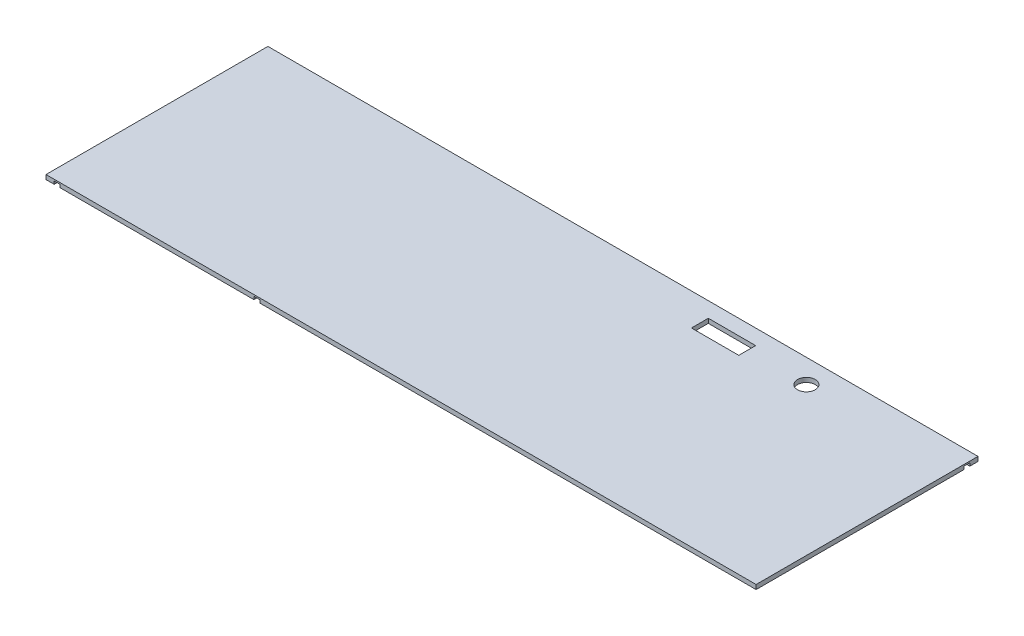
SolidWorks part; units mm, degrees
material "Oak"
ref_plane "Front Plane" through (0, 0, 0) normal (0, 0, 1) x (1, 0, 0)
ref_plane "Top Plane" through (0, 0, 0) normal (0, 1, 0) x (1, 0, 0)
ref_plane "Right Plane" through (0, 0, 0) normal (1, 0, 0) x (0, 0, -1)
sketch "Sketch1" plane through (0, 0, 0) normal (0, 1, 0) x (1, 0, 0)
  line L0 (800, 375) -> (800, -375) construction
  line L1 (-1200, -375) -> (1200, -375)
  line L2 (-1200, -375) -> (-1200, 375)
  line L3 (-1200, 375) -> (1200, 375)
  line L4 (1200, -375) -> (1200, 375)
  line L5 (-1200, -375) -> (1200, 375) construction
  line L6 (-1200, 375) -> (1200, -375) construction
  line L7 (-450, 375) -> (-450, -375) construction
  line L9 (500, 266.5) -> (340, 266.5)
  line L10 (500, 266.5) -> (500, 323.5)
  line L11 (500, 323.5) -> (340, 323.5)
  line L12 (340, 266.5) -> (340, 323.5)
  circle A0 centre (700, 295) radius 30
  point P0 (0, 0)
  point P16 (500, 295)
  dimension "D6" = 60
  dimension "D1" = 2400
  dimension "D2" = 750
  dimension "D3" = 750
  dimension "D4" = 400
  dimension "D5" = 1250
  dimension "D7" = 160
  dimension "D8" = 57
  dimension "D9" = 80
  dimension "D10" = 100
  dimension "D11" = 300
extrude "Boss-Extrude1" add sketch "Sketch1" along normal blind 15
sketch "Sketch2" plane through (0, 0, 0) normal (0, -1, 0) x (1, 0, 0)
  line L1 (-1200, -375) -> (-1125, -375) construction
  line L2 (-1200, -375) -> (-1200, -300) construction
  line L3 (-1200, -300) -> (-1125, -300) construction
  line L4 (-1125, -375) -> (-1125, -300) construction
  line L9 (-450, -375) -> (-525, -375) construction
  line L10 (-450, -375) -> (-450, -300) construction
  line L11 (-450, -300) -> (-525, -300) construction
  line L12 (-525, -375) -> (-525, -300) construction
  dimension "D1" = 75
sketch "Sketch3" plane through (0, 0, -375) normal (0, 0, -1) x (-1, 0, 0)
  line L0 (450, 0) -> (525, 0) construction
  line L1 (1125, 0) -> (1200, 0) construction
  line L2 (1162.5, 0) -> (1162.5, 15) construction
  line L3 (-1200, 15) -> (1200, 15) construction
  line L4 (487.5, 0) -> (487.5, 15) construction
  line L5 (450, 0) -> (1200, 0) construction
  line L6 (825, 0) -> (825, 15) construction
  line L7 (1152.5, 0) -> (1152.5, 10)
  line L8 (1152.5, 10) -> (1172.5, 10)
  line L9 (1172.5, 10) -> (1172.5, 0)
  line L10 (1172.5, 0) -> (1152.5, 0)
  line L11 (477.5, 10) -> (477.5, 0)
  line L12 (497.5, 10) -> (477.5, 10)
  line L13 (497.5, 0) -> (497.5, 10)
  line L14 (477.5, 0) -> (497.5, 0)
  point P0 (1125, 0)
  point P2 (450, 0)
  point P4 (525, 0)
  dimension "D1" = 20
  dimension "D2" = 10
extrude "Cut-Extrude1" cut sketch "Sketch3" against normal through all from vertex starting at point (-1200, 0, -300)
sketch "Sketch4" plane through (-1200, 0, 0) normal (-1, 0, 0) x (0, 0, 1)
  line L0 (-300, 0) -> (-375, 0) construction
  line L1 (-337.5, 0) -> (-337.5, 15) construction
  line L2 (-375, 15) -> (375, 15) construction
  line L3 (-347.5, 0) -> (-347.5, 10)
  line L4 (-347.5, 10) -> (-327.5, 10)
  line L5 (-327.5, 10) -> (-327.5, 0)
  line L6 (-327.5, 0) -> (-347.5, 0)
  line L8 (0, -7.7) -> (0, 7.7) construction
  line L9 (327.5, 10) -> (327.5, 0)
  line L10 (347.5, 10) -> (327.5, 10)
  line L11 (347.5, 0) -> (347.5, 10)
  line L12 (327.5, 0) -> (347.5, 0)
  point P0 (-300, 0)
  line M6 (-375, 0) -> (375, 0)
  dimension "D1" = 20
  dimension "D2" = 10
extrude "Cut-Extrude2" cut sketch "Sketch4" against normal up to vertex (675 mm away) from vertex contours L5 L4 L3 M6 region at (-1200, 5, -337.5) up to point (-525, 0, -300) starting at point (-1125, 0, -300)
extrude "Cut-Extrude3" cut sketch "Sketch4<4>" against normal up to vertex (2400 mm away) from vertex contours L5 L4 L3 M6 region at (-1200, 5, -337.5) up to point (1200, 0, -375) starting at point (-450, 0, -375)
sketch "Sketch4<4>" plane through (-1200, 0, 0) normal (-1, 0, 0) x (0, 0, 1) same geometry as "Sketch4"
extrude "Cut-Extrude4" cut sketch "Sketch4<5>" against normal up to vertex (2000 mm away) from vertex contours L11 L10 L9 M6 region at (-1200, 5, 337.5) up to point (800, 0, 375) starting at point (-450, 0, 375)
sketch "Sketch4<5>" plane through (-1200, 0, 0) normal (-1, 0, 0) x (0, 0, 1) same geometry as "Sketch4"
equation "\"A\"= 125cm"
equation "\"B\"= 40cm"
equation "\"C\"= 75cm"
equation "\"D\"= 15mm"
equation "\"D1@Sketch1\"=\"A\"+\"B\"+\"C\""
equation "\"D2@Sketch1\"=\"C\""
equation "\"D3@Sketch1\"=\"C\""
equation "\"D4@Sketch1\"=\"B\""
equation "\"D1@Boss-Extrude1\"=\"D\""
